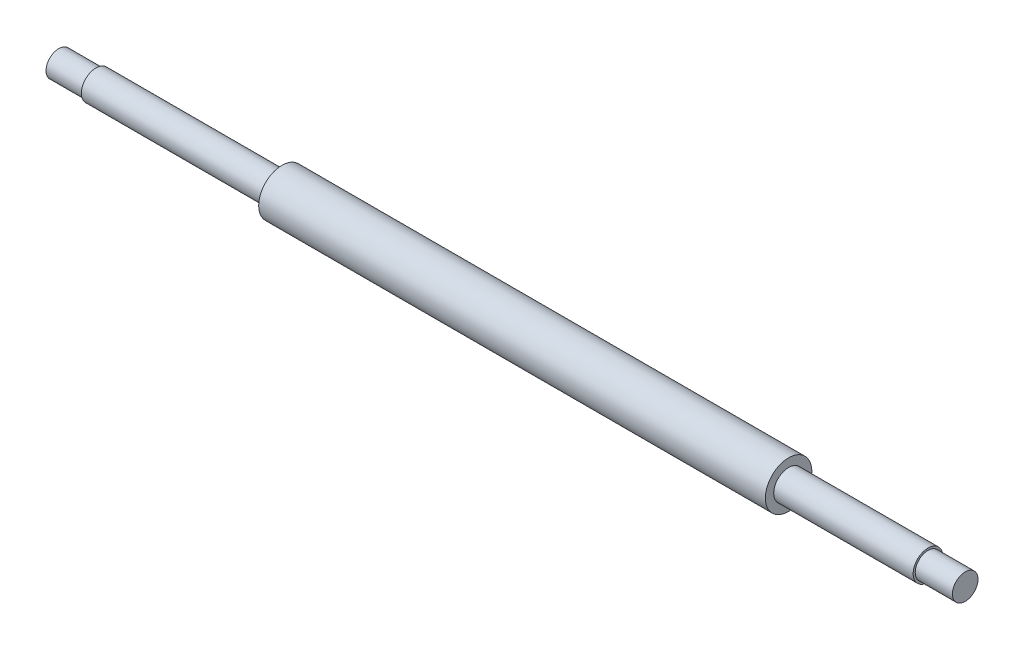
SolidWorks part; units mm, degrees
ref_plane "Front Plane" through (0, 0, 0) normal (0, 0, 1) x (1, 0, 0)
ref_plane "Top Plane" through (0, 0, 0) normal (0, 1, 0) x (1, 0, 0)
ref_plane "Right Plane" through (0, 0, 0) normal (1, 0, 0) x (0, 0, -1)
sketch "Sketch1" plane through (0, 0, 0) normal (0, 1, 0) x (1, 0, 0)
  line L0 (-77.4194, 0) -> (170.2306, 0) construction
  line L1 (-77.4194, 0) -> (-77.4194, 3.5)
  line L2 (-77.4194, 3.5) -> (-67.2594, 3.5)
  line L3 (-67.2594, 3.5) -> (-67.2594, 4)
  line L4 (-67.2594, 4) -> (-16.4594, 4)
  line L5 (-16.4594, 4) -> (-16.4594, 6.35)
  line L6 (-16.4594, 6.35) -> (121.9706, 6.35)
  line L7 (121.9706, 6.35) -> (121.9706, 4.064)
  line L8 (121.9706, 4.064) -> (160.0706, 4.064)
  line L9 (160.0706, 4.064) -> (160.0706, 3.5)
  line L10 (160.0706, 3.5) -> (170.2306, 3.5)
  line L11 (170.2306, 3.5) -> (170.2306, 0)
  line L12 (-77.4194, 0) -> (170.2306, 0)
  line L13 (-97.9506, 0) -> (194.5593, 0) construction
  dimension "D1" = 7
  dimension "D2" = 8
  dimension "D3" = 8.128
  dimension "D4" = 7
  dimension "D5" = 10.16
  dimension "D6" = 50.8
  dimension "D7" = 38.1
  dimension "D8" = 10.16
  dimension "D9" = 138.43
revolve "Revolve1" add sketch "Sketch1" angle 360 about L13
